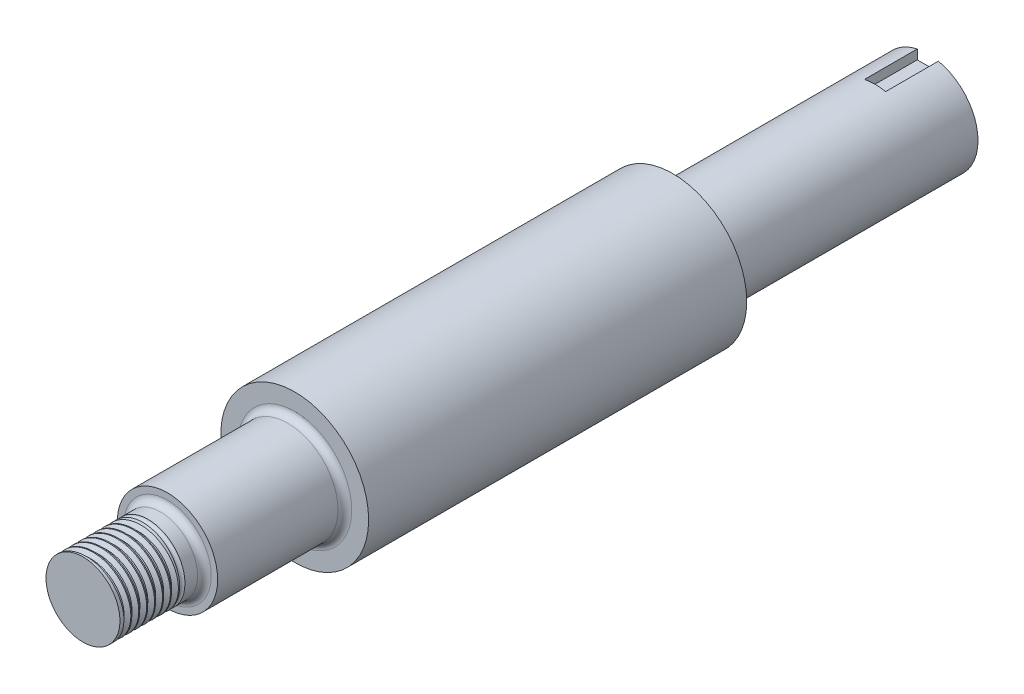
SolidWorks part; units mm, degrees
material "AISI 1020"
ref_plane "Front Plane" through (0, 0, 0) normal (0, 0, 1) x (1, 0, 0)
ref_plane "Top Plane" through (0, 0, 0) normal (0, 1, 0) x (1, 0, 0)
ref_plane "Right Plane" through (0, 0, 0) normal (1, 0, 0) x (0, 0, -1)
sketch "Sketch Spindle Skeleton" plane through (0, 0, 0) normal (1, 0, 0) x (0, 0, -1)
  line L0 (-119.9, -9.5) -> (-144, -9.5)
  line L5 (-1000, 0) -> (49000, 0)
  line L6 (0, -9.5) -> (0, 9.5)
  line L13 (0, 9.5) -> (-48.3, 9.5)
  line L26 (-48.3, 9.5) -> (-48.3, 14)
  line L27 (-48.3, 14) -> (-119.9, 14)
  line L32 (-119.9, 14) -> (-119.9, 9.5)
  line L34 (-160, 7) -> (-160, -7)
  line L36 (-119.9, -9.5) -> (-119.9, -14)
  line L37 (-119.9, -14) -> (-48.3, -14)
  line L38 (-48.3, -14) -> (-48.3, -9.5)
  line L39 (0, -9.5) -> (-48.3, -9.5)
  line L40 (-24.2, 36) -> (-19.2, 36)
  line L41 (-136.5, 22.5) -> (-119.9, 22.5)
  line L42 (-136.5, 22.5) -> (-136.5, -22.5)
  line L43 (-136.5, -22.5) -> (-119.9, -22.5)
  line L44 (-119.9, 22.5) -> (-119.9, -22.5)
  line L45 (-136.5, 22.5) -> (-119.9, -22.5) construction
  line L46 (-136.5, -22.5) -> (-119.9, 22.5) construction
  line L47 (-31.7, 22.5) -> (-48.3, 22.5)
  line L48 (-31.7, 22.5) -> (-31.7, -22.5)
  line L49 (-31.7, -22.5) -> (-48.3, -22.5)
  line L50 (-48.3, 22.5) -> (-48.3, -22.5)
  line L51 (-31.7, 22.5) -> (-48.3, -22.5) construction
  line L52 (-31.7, -22.5) -> (-48.3, 22.5) construction
  line L59 (-19.2, 36) -> (-19.2, -36)
  line L60 (-19.2, -36) -> (-24.2, -36)
  line L61 (-24.2, -22.5) -> (-29.2, -22.5)
  line L62 (-29.2, -22.5) -> (-29.2, -17.5)
  line L63 (-29.2, -17.5) -> (-24.2, -17.5)
  line L64 (-24.2, -17.5) -> (-24.2, 17.5)
  line L65 (-24.2, 17.5) -> (-29.2, 17.5)
  line L66 (-29.2, 17.5) -> (-29.2, 22.5)
  line L67 (-29.2, 22.5) -> (-24.2, 22.5)
  line L68 (-24.2, 22.5) -> (-24.2, 36)
  line L69 (-24.2, -22.5) -> (-24.2, -36)
  line L71 (-141.5, 36) -> (-25.2, 36)
  line L72 (-141.5, 36) -> (-141.5, -36)
  line L73 (-141.5, -36) -> (-25.2, -36)
  line L74 (-25.2, 36) -> (-25.2, -36)
  line L75 (-141.5, 36) -> (-25.2, -36) construction
  line L76 (-141.5, -36) -> (-25.2, 36) construction
  line L77 (-144, -9.5) -> (-144, -7)
  line L78 (-144, -7) -> (-160, -7)
  line L79 (-119.9, 9.5) -> (-144, 9.5)
  line L80 (-144, 7) -> (-160, 7)
  line L81 (-144, 9.5) -> (-144, 7)
  line L82 (-131.95, 9.5) -> (-131.95, -9.5) construction
  line L83 (-24.15, 9.5) -> (-24.15, -9.5) construction
  point P3 (0, 0)
  point P18 (-128.2, 0)
  point P24 (-40, 0)
  point P29 (-83.35, 0)
  point P48 (-19.2, 29.25)
revolve "Revolve Spindle" add sketch "Sketch Spindle Skeleton" angle 360 about L5 region at (0, 7, 84.1) region at (0, 4.75, 128.2) region at (0, 4.75, 139) region at (0, 4.75, 40) region at (0, 3.7187, 150.3817) region at (0, 4.75, 28.45) region at (0, 4.75, 24.7) region at (0, 4.75, 21.7) region at (0, 4.75, 9.6)
fillet "Bearing Rest Fillet 0.13cm " radius 1.3 3 edges at (9.5, 0, 48.3) (9.5, 0, 119.9) (7, 0, 144)
thread "Chuck Thread" pitch 1.5 method cut profile "Thread Profile2" start angle 0, offset 0, length 10, pitch 1.5, diameter 14
ref_plane "Plane2" through (-7, 0, 160) normal (0, -1, 0) x (-1, 0, 0)
sketch "Thread Profile2" plane through (-7, 0, 160) normal (0, -1, 0) x (-1, 0, 0)
  line L0 (0, 0) -> (0, 1.5) construction
  line L11 (0, 0) -> (0, 1.3125)
  line L12 (0, 1.3125) -> (-0.8119, 0.8437)
  line L13 (-0.8119, 0.8437) -> (-0.8119, 0.4687)
  line L15 (-0.8119, 0.4687) -> (0, 0)
  line L17 (-0.8119, 0.6562) -> (0, 0.6562) construction
  point P2 (0, 0)
  dimension "Pitch" = 1.5
  dimension "Profile_Angle" = 60
  dimension "Profile_Land" = 0.375
  dimension "Profile_Height" = 0.8119
sketch "Thread Slot Sketch" plane through (0, 0, 0) normal (1, 0, 0) x (0, 0, -1)
  line L0 (-148.6882, -6.0622) -> (-150.0007, -6.0622) construction
  line L1 (-148.6882, -6.0622) -> (-150.0007, -6.0622)
  line L2 (-150.0625, -7) -> (-145.3, -7) construction
  line L3 (-144, -7) -> (-160, -7) construction
  line L4 (-148.6882, -6.0622) -> (-148.6882, -7) construction
  circle A0 centre (-148.1882, -7) radius 0.5
  dimension "D1" = 1
revolve "Thread Slot" cut sketch "Thread Slot Sketch" angle 360 about L5
sketch "Sketch Key" plane through (0, 0, 0) normal (0, 0, -1) x (-1, 0, 0)
  line L0 (0, 8.5) -> (0, 0) construction
  line L1 (-2, 7.5) -> (2, 7.5)
  line L2 (-2, 7.5) -> (-2, 9.5)
  line L3 (-2, 9.5) -> (2, 9.5)
  line L4 (2, 7.5) -> (2, 9.5)
  line L5 (-2, 7.5) -> (2, 9.5) construction
  line L6 (-2, 9.5) -> (2, 7.5) construction
  circle A1 centre (0, 0) radius 9.5
  circle A2 centre (0, 0) radius 9.5
  point P0 (0, 8.5)
  dimension "D2" = 4
  dimension "D3" = 2
  dimension "D1" = 0
extrude "Key Cut" cut sketch "Sketch Key" against normal blind 10 contours L3 L4 L1 L2
